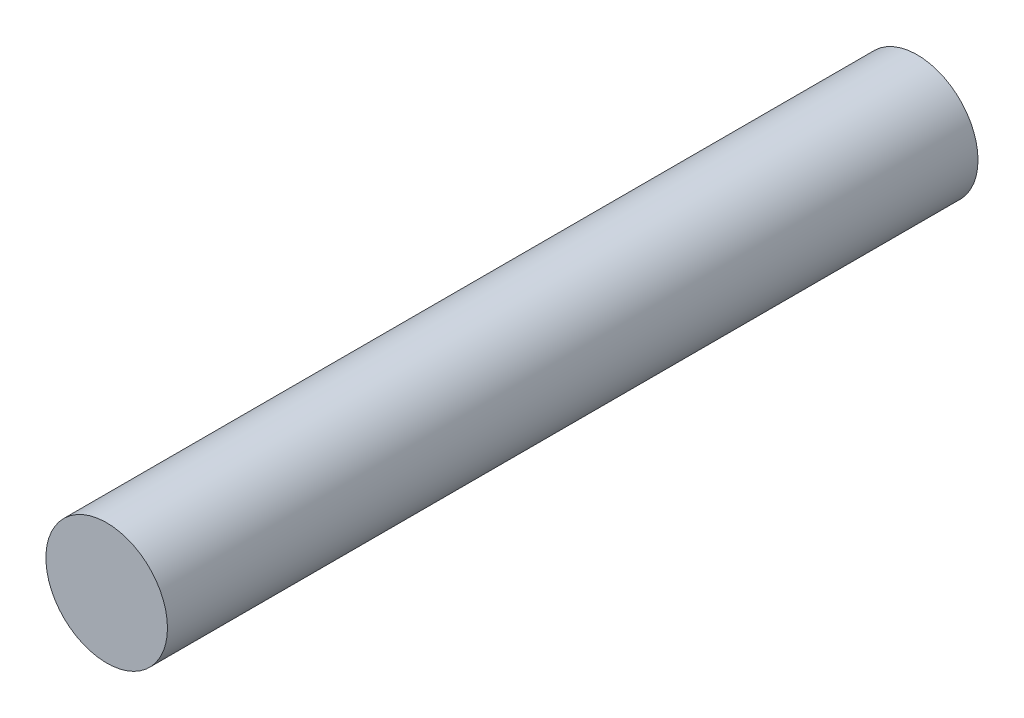
SolidWorks part; units mm, degrees
ref_plane "Front Plane" through (0, 0, 0) normal (0, 0, 1) x (1, 0, 0)
ref_plane "Top Plane" through (0, 0, 0) normal (0, 1, 0) x (1, 0, 0)
ref_plane "Right Plane" through (0, 0, 0) normal (1, 0, 0) x (0, 0, -1)
sketch "Sketch1" plane through (0, 0, 0) normal (0, 0, 1) x (1, 0, 0)
  circle A0 centre (0, 0) radius 3
  dimension "D1" = 6
extrude "Boss-Extrude1" add sketch "Sketch1" along normal blind 20 and the other way blind 20
